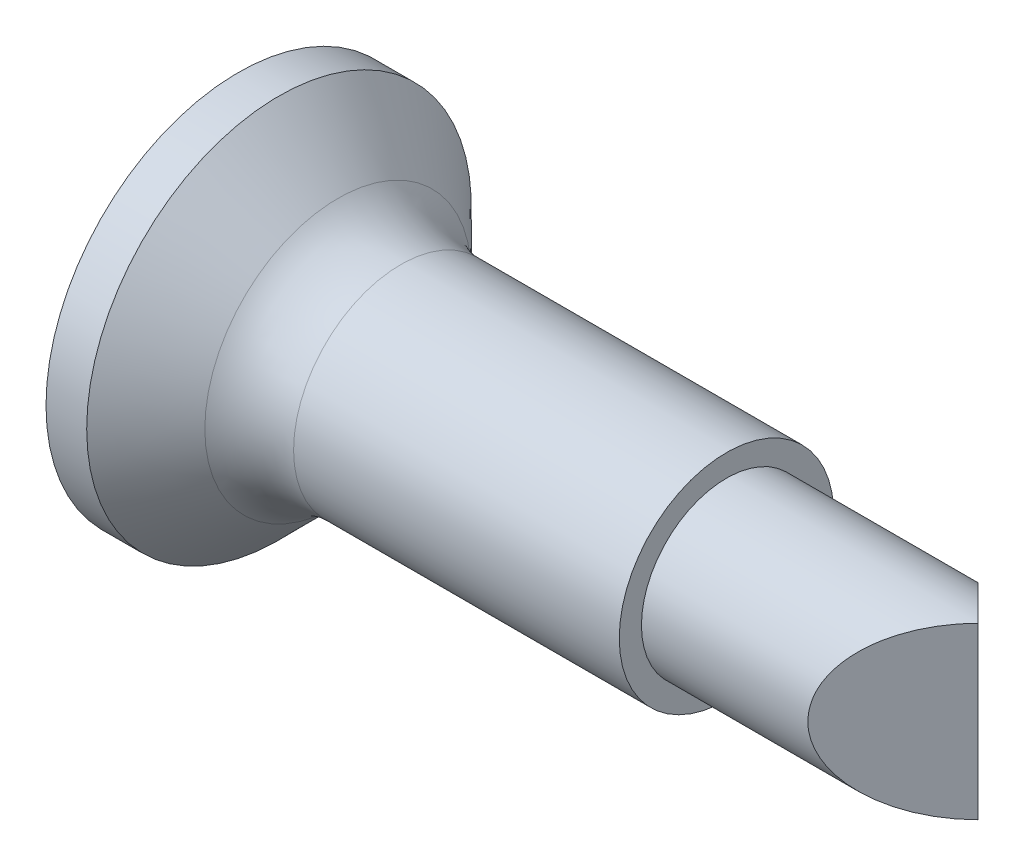
SolidWorks part; units mm, degrees
ref_plane "Front" through (0, 0, 0) normal (0, 0, 1) x (1, 0, 0)
ref_plane "Top" through (0, 0, 0) normal (0, 1, 0) x (1, 0, 0)
ref_plane "Right" through (0, 0, 0) normal (1, 0, 0) x (0, 0, -1)
sketch "Sketch1" plane through (0, 0, 0) normal (0, 0, 1) x (1, 0, 0)
  line L0 (-9.543, 0) -> (15.0934, 0) construction
  line L1 (0, 0) -> (0, 2.6)
  line L2 (0, 2.6) -> (0.55, 2.6)
  line L3 (0.55, 2.6) -> (1.7, 1.45)
  line L4 (1.7, 1.45) -> (6.6, 1.45)
  line L5 (6.6, 1.45) -> (6.6, 1.15)
  line L6 (6.6, 1.15) -> (10, 1.15)
  line L7 (10, 1.15) -> (10, 0)
  line L8 (0, 0) -> (10, 0)
  line L9 (2.8, 2.114) -> (2.8, 0.3277) construction
  dimension "D1" = 45
revolve "Base" add sketch "Sketch1" angle 360 about L0
cosmetic thread "ThreadCosmetic1" [suppressed] parameters "D1"=4.9, "D2"=2.3
fillet "Fillet1" radius 1.2 1 edges at (1.7, 0, 1.45)
sketch "Sketch2" plane through (0, 0, 0) normal (0, 1, 0) x (1, 0, 0)
  line L0 (10.757, 0) -> (13.5461, 0) construction
  line L2 (10.3703, -10) -> (10.3703, 10)
  line L3 (10.3703, 10) -> (0, 10)
  line L4 (0, 10) -> (10, 0)
  line L5 (-9.543, 0) -> (15.0934, 0) construction
  line L7 (0, -10) -> (10, 0)
  line L8 (10.3703, -10) -> (0, -10)
  line L9 (10, -1.15) -> (10, 1.15) construction
  dimension "D1" = 45
  dimension "D2" = 10
  dimension "D3" = 0.3703
extrude "Cut-Extrude1" cut sketch "Sketch2" against normal through all and the other way through all
sketch "Sketch3" plane through (0, 0, 0) normal (1, 0, 0) x (0, 0, -1)
  line L0 (-3.1307, 0) -> (3.313, 0) construction
  line L1 (0, -3.2902) -> (0, 3.0927) construction
  line L2 (-0.32, 0.32) -> (-1.6, 0.32)
  line L3 (0.32, -1.6) -> (-0.32, -1.6)
  line L4 (0.32, -1.6) -> (0.32, -0.32)
  line L5 (0.32, 1.6) -> (-0.32, 1.6)
  line L6 (-0.32, -1.6) -> (-0.32, -0.32)
  line L7 (1.6, 0.32) -> (0.32, 0.32)
  line L8 (1.6, 0.32) -> (1.6, -0.32)
  line L9 (1.6, -0.32) -> (0.32, -0.32)
  line L10 (-1.6, 0.32) -> (-1.6, -0.32)
  line L11 (-0.32, 0.32) -> (-0.32, 1.6)
  line L12 (0.32, 0.32) -> (0.32, 1.6)
  line L13 (-0.32, -0.32) -> (-1.6, -0.32)
  dimension "D1" = 3.2
  dimension "D3" = 0.64
  dimension "D4" = 0.64
extrude "CrossRecess" cut sketch "Sketch3" along normal blind 0.5667
fillet "Fillet2" radius 0.32 4 edges at (0.2833, 0.32, 0.32) (0.2833, -0.32, 0.32) (0.2833, 0.32, -0.32) (0.2833, -0.32, -0.32)
draft "Draft1" type of draft neutral plane draft angle 25 faces to draft 4 face at (0.2833, 0, 1.6) face at (0.2833, 1.6, 0) face at (0.2833, -1.6, 0) face at (0.2833, 0, -1.6) neutral plane through (0, 0, 0) neutral plane normal (-1, 0, 0) parameters "D1"=25
sketch "Sketch4" plane through (0, 0, 0) normal (1, 0, 0) x (0, 0, -1)
  line L0 (-3.0699, 0) -> (3.2219, 0) construction
  line L1 (0, -3.1383) -> (0, 3.0775) construction
  line L2 (0, 0) -> (2.9162, 2.9162) construction
  line L3 (0, 0) -> (-2.8015, 2.8015) construction
  line L4 (0, 0.4782) -> (1.1314, 1.1314)
  line L5 (1.1314, 1.1314) -> (0.4782, 0)
  line L6 (0, 0.4782) -> (-1.1314, 1.1314)
  line L7 (-1.1314, 1.1314) -> (-0.4782, 0)
  line L8 (-1.1314, -1.1314) -> (-0.4782, 0)
  line L9 (0, -0.4782) -> (-1.1314, -1.1314)
  line L10 (1.1314, -1.1314) -> (0.4782, 0)
  line L11 (0, -0.4782) -> (1.1314, -1.1314)
  dimension "D1" = 45
  dimension "D2" = 15
  dimension "D3" = 3.2
extrude "Cut-Extrude3" [suppressed] cut sketch "Sketch4" along normal blind 0.5667
sketch "Sketch5" plane through (0, 0, 0) normal (0, 0, 1) x (1, 0, 0)
  line L0 (0, 0) -> (10.3232, 0) construction
  line L1 (2.6268, 1.7964) -> (2.9732, 1.7964)
  line L2 (2.9732, 1.7964) -> (2.9732, 1.45)
  line L3 (2.9732, 1.45) -> (2.8, 1.15)
  line L4 (2.8, 1.15) -> (2.6268, 1.45)
  line L5 (2.6268, 1.45) -> (2.6268, 1.7964)
  line L6 (0, 2.6) -> (0, -2.6) construction
  dimension "D1" = 2.8
  dimension "D2" = 2.9
  dimension "D3" = 2.3
revolve "Cut-Revolve10" [suppressed] cut sketch "Sketch5" angle 360 about L0
pattern_linear "LPattern10" [suppressed] count 9 spacing 0.45 along (1, 0, 0) of bodies 105
equation "\"D1@Sketch3\" = \"m@Sketch3\""
equation "\"D4@Sketch3\" = \"D3@Sketch3\""
equation "\"D3@Sketch3\" = \"m@Sketch3\" / 5"
equation "\"D1@Fillet2\" = \"D4@Sketch3\" / 2"
equation "\"D1@Cut-Extrude3\" = \"D1@CrossRecess\""
equation "\"D1@CrossRecess\" = \"k@Sketch1\" / 3"
equation "\"D1@ThreadCosmetic1\" = \"lg@Sketch1\" - \"k@Sketch1\""
equation "\"D2@ThreadCosmetic1\" = \"dp@Sketch1\""
equation "\"D3@Sketch4\" = \"D1@Sketch3\""
equation "\"D1@Sketch5\" = \"k@Sketch1\" + \"a@Sketch1\""
equation "\"D2@Sketch5\" = \"d@Sketch1\""
equation "\"D3@Sketch5\" = \"dp@Sketch1\""
equation "\"D3@LPattern10\" =  ( \"d@Sketch1\" - \"dp@Sketch1\" )  / 2 * 1.5"
equation "\"D1@LPattern10\" = (  \"lg@Sketch1\" - \"k@Sketch1\" - \"a@Sketch1\" )  / \"D3@LPattern10\" + 1"
